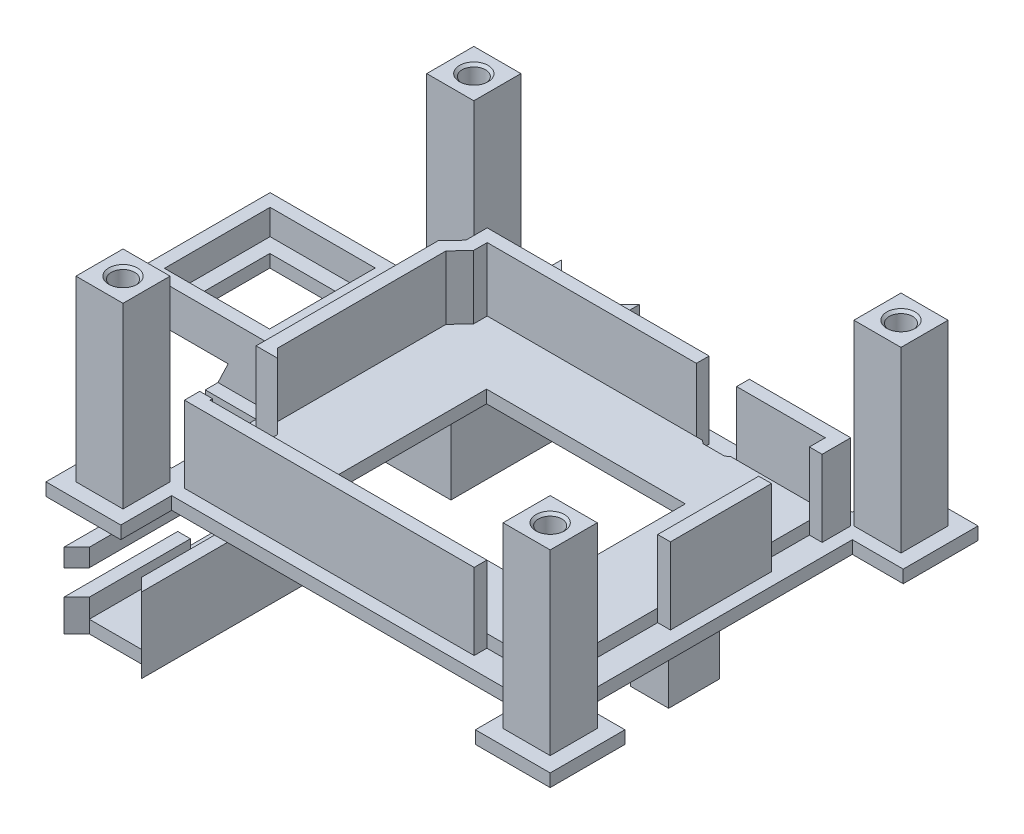
SolidWorks part; units mm, degrees
ref_plane "Front Plane" through (0, 0, 0) normal (0, 0, 1) x (1, 0, 0)
ref_plane "Top Plane" through (0, 0, 0) normal (0, 1, 0) x (1, 0, 0)
ref_plane "Right Plane" through (0, 0, 0) normal (1, 0, 0) x (0, 0, -1)
sketch "Sketch1" plane through (0, 0, 0) normal (0, -1, 0) x (1, 0, 0)
  line L0 (-32.325, 27.025) -> (34.525, 27.025)
  line L1 (34.525, 27.025) -> (34.525, -27.025)
  line L2 (34.525, -27.025) -> (-31.895, -27.025)
  line L3 (-31.895, -27.025) -> (-31.895, -24.3396)
  line L4 (-31.895, -24.3396) -> (-34.525, -21.5496)
  line L5 (-34.525, -21.5496) -> (-34.525, 11.501)
  line L6 (-34.525, 11.501) -> (-32.325, 13.751)
  line L7 (-32.325, 13.751) -> (-32.325, 27.025)
  line L8 (-32.2, 26.9) -> (34.4, 26.9) construction
  line L9 (34.4, -26.9) -> (34.4, 26.9) construction
  line L10 (16.6, -26.9) -> (34.4, -26.9) construction
  line L11 (-32.2, 13.7) -> (-32.2, 26.9) construction
  line L12 (-34.4, 11.45) -> (-32.2, 13.7) construction
  line L13 (-34.4, -21.5) -> (-34.4, 11.45) construction
  line L14 (-27.4777, 29.525) -> (37.025, 29.525)
  line L15 (37.025, 29.525) -> (37.025, -29.525)
  line L16 (37.025, -29.525) -> (-34.395, -29.525)
  line L17 (-31.77, -24.29) -> (-31.77, -26.9) construction
  line L18 (-34.4, -21.5) -> (-31.77, -24.29) construction
  line L19 (-34.395, -29.525) -> (-34.395, -25.3322)
  line L20 (-34.395, -25.3322) -> (-37.025, -22.5422)
  line L21 (-37.025, -22.5422) -> (-37.025, 14.001)
  line L22 (-37.025, 14.001) -> (-34.825, 16.251)
  line L23 (-34.825, 16.251) -> (-34.825, 29.525)
  line L24 (-34.825, 29.525) -> (-27.4777, 29.525)
  line L25 (-32.325, 26.525) -> (-34.825, 26.525)
  line L26 (9.2, -27.025) -> (17.1, -27.025)
  line L27 (9.2, -27.025) -> (9.2, -29.525)
  line L28 (9.2, -29.525) -> (17.1, -29.525)
  line L29 (17.1, -27.025) -> (17.1, -29.525)
  line L30 (-32.8139, 13.251) -> (-37.025, 13.251)
  line L32 (38.01, -14.45) -> (34.4, -14.45) construction
  line L33 (34.525, -23.9) -> (37.025, -23.9)
  line L34 (34.525, -23.9) -> (34.525, -13.95)
  line L35 (34.525, -13.95) -> (37.025, -13.95)
  line L36 (37.025, -23.9) -> (37.025, -13.95)
  line L37 (38.01, -23.4) -> (34.4, -23.4) construction
  line L38 (39.03, 17) -> (34.4, 17) construction
  line L39 (37.025, 17.5) -> (34.525, 17.5)
  line L40 (37.025, 17.5) -> (37.025, 5.9)
  line L41 (37.025, 5.9) -> (34.525, 5.9)
  line L42 (34.525, 17.5) -> (34.525, 5.9)
  line L43 (39.03, 6.4) -> (34.4, 6.4) construction
  line L44 (22.59, 26.9) -> (22.59, 22.54) construction
  line L46 (-32.325, 26.525) -> (-32.325, 16.751)
  line L48 (-34.825, 26.525) -> (-34.825, 16.751)
  line L49 (22.09, 29.525) -> (29.39, 29.525)
  line L50 (22.09, 29.525) -> (22.09, 27.025)
  line L51 (22.09, 27.025) -> (29.39, 27.025)
  line L52 (29.39, 29.525) -> (29.39, 27.025)
  line L53 (34.525, 24.8) -> (37.025, 24.8)
  line L54 (34.525, 24.8) -> (34.525, 16.8)
  line L55 (34.525, 16.8) -> (37.025, 16.8)
  line L56 (37.025, 24.8) -> (37.025, 16.8)
  line L57 (28.89, 26.9) -> (28.89, 22.54) construction
  line L58 (34.4, 24.3) -> (32.05, 24.3) construction
  line L59 (34.4, 17.3) -> (32.05, 17.3) construction
  line L72 (10.3667, -27.025) -> (11.0667, -26.5)
  line L73 (11.0667, -26.5) -> (15.2333, -26.5)
  line L74 (15.2333, -26.5) -> (15.9333, -27.025)
  line L75 (10.9, -26) -> (9.7, -26.9) construction
  line L77 (15.4, -26) -> (10.9, -26) construction
  line L79 (15.4, -26) -> (16.6, -26.9) construction
  point P72 (35.775, 24.8)
  line M6 (15.4, -26) -> (16.6, -26.9)
  line M7 (16.6, -26.9) -> (34.4, -26.9)
  line M8 (34.4, -26.9) -> (34.4, 26.9)
  line M9 (34.4, 26.9) -> (-32.2, 26.9)
  line M10 (-32.2, 26.9) -> (-32.2, 13.7)
  line M11 (-32.2, 13.7) -> (-34.4, 11.45)
  line M12 (-34.4, 11.45) -> (-34.4, -21.5)
  line M13 (-34.4, -21.5) -> (-31.77, -24.29)
  line M14 (-31.77, -24.29) -> (-31.77, -26.9)
  line M15 (-31.77, -26.9) -> (9.7, -26.9)
  line M16 (9.7, -26.9) -> (10.9, -26)
  line M17 (10.9, -26) -> (15.4, -26)
  dimension "D1" = 0.125
  dimension "D2" = 0.125
  dimension "D3" = 0.125
  dimension "D4" = 0.125
  dimension "D5" = 0.125
  dimension "D6" = 0.125
  dimension "D7" = 0.125
  dimension "D8" = 0.125
  dimension "D9" = 2.5
  dimension "D10" = 2.5
  dimension "D11" = 2.5
  dimension "D12" = 2.5
  dimension "D13" = 2.5
  dimension "D14" = 2.5
  dimension "D15" = 2.5
  dimension "D16" = 2.5
  dimension "D17" = 2.5
  dimension "D19" = 0.5
  dimension "D18" = 0.5
  dimension "D20" = 0.5
  dimension "D21" = 0.5
  dimension "D22" = 0.5
  dimension "D23" = 0.5
  dimension "D26" = 0.5
  dimension "D27" = 0.5
  dimension "D28" = 0.5
  dimension "D29" = 0.5
  dimension "D30" = 0.5
  dimension "D31" = 0.5
  dimension "D32" = 0.5
  dimension "D24" = 0.5
  dimension "D25" = 0.5
extrude "Boss-Extrude4" add sketch "Sketch1" along normal blind 2.5 contours L7 L23 L22 L21 L20 L19 L16 L27 L2 L3 L4 L5 L6 | L7 L0 L1 L39 L15 L14 L24 L23 | L33 L1 L2 L29 L16 L15 | L15 L41 L1 L35 | L1 L53 L15 L14 L52 L0 | M17 M6 M7 M8 M9 M10 M11 M12 M13 M14 M15 M16 | L7 L6 L5 L4 L3 L2 L1 L42 L0 M6 M17 M16 M15 M14 M13 M12 M11 M10 M9 M8 M7 region at (-6.6044, 0, 28.2619) region at (-5.1175, 0, 26.9373) region at (33.7869, 0, 27.7419) region at (-34.1198, 0, 12.8163) region at (35.775, 0, -4.025) region at (28.2437, 0, -27.8937) region at (0.3648, 0, -0.0614)
extrude "Boss-Extrude5" add sketch "Sketch1<5>" against normal blind 12.5 contours L24 L23 L22 L21 L20 L19 L16 L15 L14 L6 L7 L0 L1 L2 L3 L4 L5 | L50 L14 L24 L23 L25 L7 L0 | L1 L53 L15 L14 L52 L0 | L15 L41 L1 L35 | L33 L1 L2 L29 L16 L15 region at (-6.6044, 0, 28.2619) region at (33.7869, 0, 27.7419) region at (-34.1198, 0, 12.8163) region at (35.775, 0, -4.025) region at (28.2437, 0, -27.8937)
sketch "Sketch1<5>" plane through (0, 0, 0) normal (0, -1, 0) x (1, 0, 0) same geometry as "Sketch1"
sketch "Sketch2" plane through (0, 0, 0) normal (0, 1, 0) x (1, 0, 0)
  line L22 (22.09, -24.525) -> (29.39, -24.525)
  line L23 (22.09, -24.525) -> (29.39, -24.525)
  line L24 (17.1, 24.525) -> (16.7667, 24.525)
  line L25 (17.1, 24.525) -> (16.7667, 24.525)
  line L26 (9.2, 24.525) -> (-29.395, 24.525)
  line L27 (9.2, 24.525) -> (-29.395, 24.525)
  line L28 (-31.0264, -11.5032) -> (-29.825, -12.7318)
  line L29 (-31.0264, -11.5032) -> (-29.825, -12.7318)
  line L30 (32.025, 13.95) -> (32.025, 23.9)
  line L31 (32.025, 13.95) -> (32.025, 23.9)
  line L32 (32.025, 23.9) -> (32.025, 24.525)
  line L33 (32.025, 23.9) -> (32.025, 24.525)
  line L34 (32.025, 24.525) -> (17.1, 24.525)
  line L35 (32.025, 24.525) -> (17.1, 24.525)
  line L36 (-29.825, -24.525) -> (22.09, -24.525)
  line L37 (-29.825, -24.525) -> (22.09, -24.525)
  line L38 (32.025, -24.525) -> (32.025, -5.9)
  line L39 (32.025, -24.525) -> (32.025, -5.9)
  line L40 (32.025, -5.9) -> (32.025, 13.95)
  line L41 (32.025, -5.9) -> (32.025, 13.95)
  line L181 (29.39, -24.525) -> (32.025, -24.525)
  line L184 (16.7667, 24.525) -> (16.0667, 24)
  line L185 (16.0667, 24) -> (10.2333, 24)
  line L186 (10.2333, 24) -> (9.5333, 24.525)
  line L187 (9.5333, 24.525) -> (9.2, 24.525)
  line L188 (-29.395, 24.525) -> (-29.395, 23.3471)
  line L190 (-29.395, 23.3471) -> (-32.025, 20.5571)
  line L191 (-32.025, 20.5571) -> (-32.025, -10.4818)
  line L192 (-32.025, -10.4818) -> (-31.0264, -11.5032)
  line L193 (-29.825, -12.7318) -> (-29.825, -24.525)
  line L195 (29.39, -24.525) -> (32.025, -24.525)
  line L198 (16.7667, 24.525) -> (16.0667, 24)
  line L199 (16.0667, 24) -> (10.2333, 24)
  line L200 (10.2333, 24) -> (9.5333, 24.525)
  line L201 (9.5333, 24.525) -> (9.2, 24.525)
  line L202 (-29.395, 24.525) -> (-29.395, 23.3471)
  line L204 (-29.395, 23.3471) -> (-32.025, 20.5571)
  line L205 (-32.025, 20.5571) -> (-32.025, -10.4818)
  line L206 (-32.025, -10.4818) -> (-31.0264, -11.5032)
  line L207 (-29.825, -12.7318) -> (-29.825, -24.525)
  line L209 (-19.525, -14.525) -> (19.525, -14.525)
  line L210 (-19.525, -14.525) -> (-19.525, 14.525)
  line L211 (-19.525, 14.525) -> (19.525, 14.525)
  line L212 (19.525, -14.525) -> (19.525, 14.525)
  line L213 (-19.525, -14.525) -> (19.525, 14.525) construction
  line L214 (-19.525, 14.525) -> (19.525, -14.525) construction
  point P2 (0, 0)
  dimension "D1" = 2.5
extrude "Cut-Extrude1" cut sketch "Sketch2" against normal blind 12.5 contours L209 L212 L211 L210 region at (0, 0, 0)
sketch "Sketch3" plane through (0, 0, 0) normal (0, 1, 0) x (1, 0, 0)
  line L12 (-41.9, -5.7344) -> (-41.9, 15.0256)
  line L13 (-41.9, 15.0256) -> (-62.55, 15.0256)
  line L14 (-62.55, 15.0256) -> (-62.55, -5.7344)
  line L15 (-62.55, -5.7344) -> (-41.9, -5.7344)
  line L16 (-41.9, -5.7344) -> (-41.9, 15.0256)
  line L17 (-41.9, 15.0256) -> (-62.55, 15.0256)
  line L18 (-62.55, 15.0256) -> (-62.55, -5.7344)
  line L19 (-62.55, -5.7344) -> (-41.9, -5.7344)
  line L24 (-39.4, -8.2344) -> (-39.4, 17.5256)
  line L25 (-39.4, 17.5256) -> (-65.05, 17.5256)
  line L26 (-65.05, 17.5256) -> (-65.05, -8.2344)
  line L27 (-65.05, -8.2344) -> (-39.4, -8.2344)
  line L28 (-39.4, -8.2344) -> (-39.4, 17.5256)
  line L29 (-39.4, 17.5256) -> (-65.05, 17.5256)
  line L30 (-65.05, 17.5256) -> (-65.05, -8.2344)
  line L31 (-65.05, -8.2344) -> (-39.4, -8.2344)
  dimension "D1" = 0.125
  dimension "D2" = 2.625
extrude "Boss-Extrude6" add sketch "Sketch3" along normal up to surface (4.175 mm away) separate body contours L18 L19 L16 L17 | L30 L31 L28 L29 L19 L18 L17 L16 region at (-52.225, 0, -4.6456) region at (-52.225, 0, 7.8709)
extrude "Boss-Extrude7" add sketch "Sketch3<3>" along normal blind 9.17
sketch "Sketch3<3>" plane through (0, 0, 0) normal (0, 1, 0) x (1, 0, 0) same geometry as "Sketch3"
sketch "Sketch5" plane through (0, 0, 0) normal (0, -1, 0) x (1, 0, 0)
  line L1 (-65.05, 8.2344) -> (-39.4, 8.2344)
  line L2 (-65.05, 8.2344) -> (-65.05, -17.5256)
  line L3 (-65.05, -17.5256) -> (-39.4, -17.5256)
  line L4 (-39.4, 8.2344) -> (-39.4, -17.5256)
extrude "Cut-Extrude2" cut sketch "Sketch5" against normal blind 1.68
sketch "Sketch6" plane through (0, 1.68, 0) normal (0, -1, 0) x (1, 0, 0)
  line L0 (-65.05, -4.6456) -> (-39.4, -4.6456) construction
  line L1 (-59.725, -12.1456) -> (-44.725, -12.1456)
  line L2 (-59.725, -12.1456) -> (-59.725, 2.8544)
  line L3 (-59.725, 2.8544) -> (-44.725, 2.8544)
  line L4 (-44.725, -12.1456) -> (-44.725, 2.8544)
  line L5 (-59.725, -12.1456) -> (-44.725, 2.8544) construction
  line L6 (-59.725, 2.8544) -> (-44.725, -12.1456) construction
  line L7 (-65.05, 8.2344) -> (-65.05, -17.5256) construction
  line L8 (-39.4, -17.5256) -> (-39.4, 8.2344) construction
  line L9 (-52.225, 8.2344) -> (-52.225, -17.5256) construction
  line L10 (-39.4, 8.2344) -> (-65.05, 8.2344) construction
  line L11 (-65.05, -17.5256) -> (-39.4, -17.5256) construction
  point P0 (-52.225, -4.6456)
  point P18 (-52.225, -4.6456)
  dimension "D1" = 15
extrude "Cut-Extrude3" cut sketch "Sketch6" against normal up to next (2.495 mm away)
sketch "Sketch7" plane through (-39.4, 0, 0) normal (1, 0, 0) x (0, 0, -1)
  line L0 (-8.2344, 9.17) -> (17.5256, 9.17) construction
  line L1 (-8.2344, 9.17) -> (17.5256, 9.17)
  line L2 (-8.2344, 9.17) -> (-8.2344, 1.68)
  line L3 (-8.2344, 1.68) -> (17.5256, 1.68)
  line L4 (17.5256, 9.17) -> (17.5256, 1.68)
  line L5 (-8.2344, 9.17) -> (-8.2344, 1.68) construction
extrude "Boss-Extrude8" add sketch "Sketch7" along normal up to next
sketch "Sketch8" plane through (0, -2.5, 0) normal (0, -1, 0) x (1, 0, 0)
  line L31 (-34.825, 29.525) -> (22.09, 29.525) construction
  line L32 (-49.525, -42.025) -> (49.525, -42.025)
  line L33 (-49.525, -42.025) -> (-49.525, 42.025)
  line L34 (-49.525, 42.025) -> (49.525, 42.025)
  line L35 (49.525, -42.025) -> (49.525, 42.025)
  line L36 (-49.525, -42.025) -> (49.525, 42.025) construction
  line L37 (-49.525, 42.025) -> (49.525, -42.025) construction
  line L39 (37.025, 5.9) -> (37.025, -13.95) construction
  line L40 (19.525, 14.525) -> (-19.525, 14.525) construction
  line L41 (-24.525, 19.525) -> (24.525, 19.525)
  line L42 (-24.525, 19.525) -> (-24.525, -19.525)
  line L43 (-24.525, -19.525) -> (24.525, -19.525)
  line L44 (24.525, 19.525) -> (24.525, -19.525)
  line L45 (-24.525, 19.525) -> (24.525, -19.525) construction
  line L46 (-24.525, -19.525) -> (24.525, 19.525) construction
  line L47 (19.525, -14.525) -> (19.525, 14.525) construction
  point P2 (0, 0)
  point P7 (0, 0)
  dimension "D1" = 12.5
  dimension "D2" = 12.5
  dimension "D3" = 5
  dimension "D4" = 5
extrude "Boss-Extrude10" add sketch "Sketch8" along normal blind 2.5
sketch "Sketch9" plane through (0, 0, -17.5256) normal (0, 0, -1) x (-1, 0, 0)
  line L0 (47.5344, 1.68) -> (37.025, 1.68)
  line L2 (37.025, 1.68) -> (37.025, -2.5)
  line L3 (49.525, -2.5) -> (-49.525, -2.5) construction
  line L4 (49.525, -2.5) -> (47.5344, 1.68)
  line L5 (37.025, -2.5) -> (37.025, 12.5) construction
  line L6 (37.025, -2.5) -> (49.525, -2.5)
extrude "Boss-Extrude11" add sketch "Sketch9" against normal up to surface (25.76 mm away) up to face at (-51.0375, 5.425, 8.2344)
sketch "Sketch10" plane through (0, -2.5, 0) normal (0, 1, 0) x (1, 0, 0)
  line L0 (-34.395, 29.525) -> (-34.395, 25.3322) construction
  line L1 (-46.585, 29.835) -> (-37.335, 29.835)
  line L2 (-46.585, 29.835) -> (-46.585, 39.085)
  line L3 (-46.585, 39.085) -> (-37.335, 39.085)
  line L4 (-37.335, 29.835) -> (-37.335, 39.085)
  line L5 (-46.585, 29.835) -> (-37.335, 39.085) construction
  line L6 (-46.585, 39.085) -> (-37.335, 29.835) construction
  line L7 (-49.525, 42.025) -> (-34.395, 42.025)
  line L8 (-49.525, 42.025) -> (-49.525, 26.895)
  line L9 (-49.525, 26.895) -> (-34.395, 26.895)
  line L10 (-34.395, 42.025) -> (-34.395, 26.895)
  line L11 (-41.96, 26.895) -> (-41.96, 42.025) construction
  line L12 (-49.525, 34.46) -> (-34.395, 34.46) construction
  line L13 (0, 42.025) -> (0, -42.025) construction
  line L14 (-49.525, 42.025) -> (49.525, 42.025) construction
  line L15 (49.525, -42.025) -> (-49.525, -42.025) construction
  line L16 (49.525, 0) -> (-42.025, 0) construction
  line L17 (49.525, 42.025) -> (49.525, -42.025) construction
  line L18 (-42.025, -5.6094) -> (-42.025, 14.9006) construction
  line L19 (46.585, 29.835) -> (37.335, 29.835)
  line L20 (46.585, 29.835) -> (46.585, 39.085)
  line L21 (46.585, 39.085) -> (37.335, 39.085)
  line L22 (37.335, 29.835) -> (37.335, 39.085)
  line L23 (-46.585, -29.835) -> (-37.335, -29.835)
  line L24 (-37.335, -29.835) -> (-37.335, -39.085)
  line L25 (-46.585, -39.085) -> (-37.335, -39.085)
  line L26 (-46.585, -29.835) -> (-46.585, -39.085)
  line L27 (46.585, -29.835) -> (37.335, -29.835)
  line L28 (37.335, -29.835) -> (37.335, -39.085)
  line L29 (46.585, -39.085) -> (37.335, -39.085)
  line L30 (46.585, -29.835) -> (46.585, -39.085)
  line L32 (-37.335, 39.085) -> (37.335, 39.085)
  line L33 (-37.335, 39.085) -> (-37.335, 29.835)
  line L34 (-37.335, 29.835) -> (37.335, 29.835)
  line L35 (37.335, 39.085) -> (37.335, 29.835)
  line L36 (0, 29.835) -> (0, 39.085) construction
  line L37 (-37.335, 34.46) -> (37.335, 34.46) construction
  line L38 (-37.335, -29.835) -> (37.335, -29.835)
  line L39 (-37.335, -29.835) -> (-37.335, -39.085)
  line L40 (-37.335, -39.085) -> (37.335, -39.085)
  line L41 (37.335, -29.835) -> (37.335, -39.085)
  line L42 (0, -39.085) -> (0, -29.835) construction
  line L43 (-37.335, -34.46) -> (37.335, -34.46) construction
  point P0 (-41.96, 34.46)
  point P204 (0, 34.46)
  point P209 (0, -34.46)
  point P993 (-41.96, 34.46)
  line M21 (17.1, 29.525) -> (37.025, 29.525)
  line M22 (37.025, 29.525) -> (37.025, 23.9)
  line M30 (37.025, -24.8) -> (37.025, -29.525)
  line M31 (37.025, -29.525) -> (29.39, -29.525)
  dimension "D1" = 9.25
  dimension "D2" = 9.25
extrude "Boss-Extrude12" add sketch "Sketch10" along normal blind 35 contours L1 L4 L3 L2 | L22 L19 L20 L21 M21 M22 | L30 L27 L28 L29 M30 M31 | L23 L26 L25 L24 region at (-41.96, -2.5, -34.46) region at (41.96, -2.5, -34.46) region at (-41.96, -2.5, 34.46) region at (41.96, -2.5, 34.46)
sketch "Sketch11" plane through (0, 32.5, 0) normal (0, 1, 0) x (1, 0, 0)
  line L0 (-41.96, 39.085) -> (-41.96, 29.835)
  line L1 (-46.585, 39.085) -> (-37.335, 39.085) construction
  line L2 (-46.585, 29.835) -> (-37.335, 29.835) construction
  line L3 (-44.26, 34.46) -> (-44.26, 39.085)
  line L4 (-46.585, 29.835) -> (-46.585, 39.085) construction
  line L5 (-46.585, 34.46) -> (-37.335, 34.46)
  line L6 (-37.335, 29.835) -> (-37.335, 39.085) construction
  line L7 (-81.725, 0) -> (81.725, 0) construction
  line L8 (0, 67.5081) -> (0, -67.5081) construction
  circle A0 centre (-41.96, 34.46) radius 2.3
  circle A1 centre (41.96, 34.46) radius 2.3
  circle A2 centre (41.96, -34.46) radius 2.3
  circle A3 centre (-41.96, -34.46) radius 2.3
  point P20 (0, 0)
  point P24 (0, 0)
  dimension "D1" = 4.6
extrude "Cut-Extrude5" cut sketch "Sketch11" against normal blind 6.2 contours L5 A0 L0 | L0 A0 L5 | L5 A0 L0 | L0 A0 L5 | A3 | A2 | A1 region at (-40.9838, 32.5, -35.4362) region at (-42.9362, 32.5, -35.4362) region at (-40.9838, 32.5, -33.4838) region at (-42.9362, 32.5, -33.4838) region at (41.96, 32.5, -34.46) region at (41.96, 32.5, 34.46) region at (-41.96, 32.5, 34.46)
chamfer "Chamfer3" distance 0.5 angle 45 4 edges at (41.96, 32.5, 36.76) (41.96, 32.5, -32.16) (-41.96, 32.5, -32.16) (-41.96, 32.5, 36.76)
sketch "Sketch13" plane through (0, -2.5, 0) normal (0, 1, 0) x (1, 0, 0)
  line L0 (-49.525, 42.025) -> (49.525, 42.025) construction
  line L1 (-34.835, 42.025) -> (34.835, 42.025)
  line L2 (-34.835, 42.025) -> (-34.835, 32.025)
  line L3 (-34.835, 32.025) -> (34.835, 32.025)
  line L4 (34.835, 42.025) -> (34.835, 32.025)
  line L5 (0, 32.025) -> (0, 42.025) construction
  line L6 (-34.835, 37.025) -> (34.835, 37.025) construction
  line L7 (39.525, 27.335) -> (49.525, 27.335)
  line L8 (39.525, 27.335) -> (39.525, -27.335)
  line L9 (39.525, -27.335) -> (49.525, -27.335)
  line L10 (49.525, 27.335) -> (49.525, -27.335)
  line L11 (44.525, -27.335) -> (44.525, 27.335) construction
  line L12 (39.525, 0) -> (49.525, 0) construction
  line L13 (-34.835, -32.025) -> (34.835, -32.025)
  line L14 (-34.835, -32.025) -> (-34.835, -42.025)
  line L15 (-34.835, -42.025) -> (34.835, -42.025)
  line L16 (34.835, -32.025) -> (34.835, -42.025)
  line L17 (0, -42.025) -> (0, -32.025) construction
  line L18 (-34.835, -37.025) -> (34.835, -37.025) construction
  line L19 (-49.525, -10.7344) -> (-39.525, -10.7344)
  line L20 (-49.525, -10.7344) -> (-49.525, -27.335)
  line L21 (-49.525, -27.335) -> (-39.525, -27.335)
  line L22 (-39.525, -10.7344) -> (-39.525, -27.335)
  line L23 (-44.525, -27.335) -> (-44.525, -10.7344) construction
  line L24 (-49.525, -19.0347) -> (-39.525, -19.0347) construction
  line L25 (-49.525, 27.335) -> (-39.525, 27.335)
  line L26 (-49.525, 27.335) -> (-49.525, 20.0256)
  line L27 (-49.525, 20.0256) -> (-39.525, 20.0256)
  line L28 (-39.525, 27.335) -> (-39.525, 20.0256)
  line L29 (-44.525, 20.0256) -> (-44.525, 27.335) construction
  line L30 (-49.525, 23.6803) -> (-39.525, 23.6803) construction
  line L31 (9.2, 29.525) -> (-34.395, 29.525) construction
  line L32 (-37.335, 29.835) -> (-37.335, 39.085) construction
  line L33 (37.335, 29.835) -> (37.335, 39.085) construction
  line L34 (49.525, 42.025) -> (49.525, -42.025) construction
  line L35 (46.585, 29.835) -> (37.335, 29.835) construction
  line L36 (46.585, -29.835) -> (37.335, -29.835) construction
  line L37 (37.025, 23.9) -> (37.025, 29.525) construction
  line L38 (37.335, -29.835) -> (37.335, -39.085) construction
  line L39 (-34.825, -29.525) -> (22.09, -29.525) construction
  line L40 (-37.335, -29.835) -> (-37.335, -39.085) construction
  line L41 (49.525, -42.025) -> (-49.525, -42.025) construction
  line L42 (-49.525, -42.025) -> (-49.525, -8.2344) construction
  line L43 (-37.025, 22.5422) -> (-37.025, -13.251) construction
  line L44 (-46.585, -29.835) -> (-37.335, -29.835) construction
  line L45 (-49.525, -8.2344) -> (-37.025, -8.2344) construction
  line L46 (-37.025, 17.5256) -> (-49.525, 17.5256) construction
  line L47 (-46.585, 29.835) -> (-37.335, 29.835) construction
  line L48 (-37.025, 22.5422) -> (-37.025, 17.5256) construction
  line L49 (-49.525, 17.5256) -> (-49.525, 42.025) construction
  point P80 (-44.525, 23.6803)
  point P104 (44.525, 0)
  point P116 (0, 37.025)
  point P138 (0, -37.025)
  point P155 (-44.525, -19.0347)
  dimension "D1" = 0
  dimension "D2" = 2.5
  dimension "D3" = 2.5
  dimension "D4" = 2.5
  dimension "D5" = 0
  dimension "D6" = 2.5
  dimension "D7" = 2.5
  dimension "D8" = 2.5
  dimension "D9" = 2.5
  dimension "D10" = 2.5
  dimension "D11" = 2.5
  dimension "D12" = 0
  dimension "D13" = 0
  dimension "D14" = 2.5
  dimension "D15" = 2.5
  dimension "D16" = 2.5
  dimension "D17" = 2.5
  dimension "D18" = 2.5
  dimension "D19" = 2.5
  dimension "D20" = 0
extrude "Cut-Extrude6" cut sketch "Sketch13" against normal blind 10
sketch "Sketch14" plane through (0, -5, 0) normal (0, -1, 0) x (1, 0, 0)
  line L1 (-39.15, 48.9) -> (-39.15, 11.9)
  line L2 (-39.15, 11.9) -> (-23.9, 11.9)
  line L3 (-23.9, 11.9) -> (-23.9, 48.9)
  line L8 (-39.15, -11.9) -> (-39.15, -48.9)
  line L10 (-23.9, -48.9) -> (-23.9, -11.9)
  line L11 (-23.9, -11.9) -> (-39.15, -11.9)
  line L12 (-36.65, -46.4) -> (-26.4, -46.4)
  line L13 (-26.4, -46.4) -> (-26.4, -14.4)
  line L14 (-26.4, -14.4) -> (-36.65, -14.4)
  line L15 (-36.65, -14.4) -> (-36.65, -46.4)
  line L16 (-26.4, 46.4) -> (-36.65, 46.4)
  line L17 (-36.65, 46.4) -> (-36.65, 14.4)
  line L18 (-36.65, 14.4) -> (-26.4, 14.4)
  line L19 (-26.4, 14.4) -> (-26.4, 46.4)
  line L21 (-36.65, 46.4) -> (-36.65, 14.4)
  line L22 (-36.65, 14.4) -> (-26.4, 14.4)
  line L23 (-26.4, 14.4) -> (-26.4, 46.4)
  line L25 (-26.4, -46.4) -> (-26.4, -14.4)
  line L26 (-26.4, -14.4) -> (-36.65, -14.4)
  line L27 (-36.65, -14.4) -> (-36.65, -46.4)
  line L44 (-23.9, 48.9) -> (-39.15, 48.9) construction
  line L45 (-26.4, 46.4) -> (-36.65, 46.4) construction
  line L46 (-39.15, 48.9) -> (-36.65, 46.4)
  line L47 (-26.4, 46.4) -> (-23.9, 48.9)
  line L48 (-26.4, -46.4) -> (-23.9, -48.9)
  line L49 (-39.15, -48.9) -> (-23.9, -48.9) construction
  line L50 (-36.65, -46.4) -> (-26.4, -46.4) construction
  line L51 (-36.65, -46.4) -> (-39.15, -48.9)
  dimension "D1" = 0.125
  dimension "D2" = 2.5
  dimension "D3" = 0.125
  dimension "D4" = 2.5
extrude "Boss-Extrude13" add sketch "Sketch14" along normal blind 12.25
sketch "Sketch16" plane through (0, -17.25, 0) normal (0, -1, 0) x (1, 0, 0)
  line L0 (-39.15, 48.9) -> (-36.65, 46.4)
  line L1 (-36.65, 46.4) -> (-36.65, 14.4)
  line L2 (-36.65, 14.4) -> (-26.4, 14.4)
  line L3 (-26.4, 14.4) -> (-26.4, 46.4)
  line L4 (-26.4, 46.4) -> (-23.9, 48.9)
  line L5 (-23.9, 48.9) -> (-23.9, 11.9)
  line L6 (-39.15, 11.9) -> (-23.9, 11.9) construction
  line L7 (-23.9, 11.9) -> (-23.9, 48.9) construction
  line L8 (-23.9, 11.9) -> (-39.15, 11.9)
  line L9 (-39.15, 48.9) -> (-39.15, 11.9) construction
  line L18 (-36.65, -46.4) -> (-26.4, -46.4)
  line L19 (-36.65, 46.4) -> (-26.4, 46.4)
  line L26 (-23.9, -11.9) -> (-39.15, -11.9)
  line L27 (-39.15, -11.9) -> (-39.15, -48.9)
  line L28 (-39.15, -48.9) -> (-36.65, -46.4)
  line L29 (-36.65, -46.4) -> (-36.65, -14.4)
  line L30 (-36.65, -14.4) -> (-26.4, -14.4)
  line L31 (-26.4, -14.4) -> (-26.4, -46.4)
  line L32 (-26.4, -46.4) -> (-23.9, -48.9)
  line L33 (-23.9, -48.9) -> (-23.9, -11.9)
  line L34 (-23.9, -11.9) -> (-39.15, -11.9)
  line L35 (-39.15, -11.9) -> (-39.15, -48.9)
  line L36 (-39.15, -48.9) -> (-36.65, -46.4)
  line L37 (-36.65, -46.4) -> (-36.65, -14.4)
  line L38 (-36.65, -14.4) -> (-26.4, -14.4)
  line L39 (-26.4, -14.4) -> (-26.4, -46.4)
  line L40 (-26.4, -46.4) -> (-23.9, -48.9)
  line L41 (-23.9, -48.9) -> (-23.9, -11.9)
  line M9 (-23.9, 48.9) -> (-26.4, 46.4)
  line M10 (-26.4, 46.4) -> (-26.4, 14.4)
  line M11 (-26.4, 14.4) -> (-36.65, 14.4)
  line M12 (-36.65, 14.4) -> (-36.65, 46.4)
  line M13 (-36.65, 46.4) -> (-39.15, 48.9)
  line M14 (-39.15, 48.9) -> (-39.15, 11.9)
  line M15 (-39.15, 11.9) -> (-23.9, 11.9)
  line M16 (-23.9, 11.9) -> (-23.9, 48.9)
  dimension "D1" = 0
extrude "Boss-Extrude15" add sketch "Sketch16" along normal blind 2.5 contours M16 M9 M10 M11 M12 M13 M14 M15 | L40 L41 L34 L35 L36 L37 L38 L39 | L19 M12 M11 M10 | L39 L38 L37 L18 region at (-38.183, -17.25, 47.367) region at (-31.525, -17.25, 30.4) region at (-31.525, -17.25, -30.4) region at (-38.183, -17.25, -47.367)
sketch "Sketch18" plane through (-36.525, 0, 0) normal (-1, 0, 0) x (0, 0, 1)
  line L0 (-14.525, -17.125) -> (-46.275, -17.125) construction
  line L1 (-17.525, -17.125) -> (-26.525, -17.125)
  line L2 (-17.525, -17.125) -> (-17.525, -5.125)
  line L3 (-17.525, -5.125) -> (-26.525, -5.125)
  line L4 (-26.525, -17.125) -> (-26.525, -5.125)
  line L5 (-22.025, -5.125) -> (-22.025, -17.125) construction
  line L6 (-17.525, -11.125) -> (-26.525, -11.125) construction
  line L7 (-14.525, -5.125) -> (-46.275, -5.125) construction
  line L8 (46.275, -17.125) -> (14.525, -17.125) construction
  line L9 (26.525, -17.125) -> (17.525, -17.125)
  line L10 (26.525, -17.125) -> (26.525, -5.125)
  line L11 (26.525, -5.125) -> (17.525, -5.125)
  line L12 (17.525, -17.125) -> (17.525, -5.125)
  line L13 (22.025, -5.125) -> (22.025, -17.125) construction
  line L14 (26.525, -11.125) -> (17.525, -11.125) construction
  line L15 (46.275, -5.125) -> (14.525, -5.125) construction
  line L16 (-14.525, -17.125) -> (-14.525, -5.125) construction
  line L17 (14.525, -17.125) -> (14.525, -5.125) construction
  point P232 (22.025, -11.125)
  point P292 (-22.025, -11.125)
  dimension "D1" = 3
  dimension "D2" = 3
  dimension "D3" = 12
  dimension "D4" = 12
extrude "Cut-Extrude9" cut sketch "Sketch18" along normal through all
sketch "Sketch21" plane through (-39.15, 0, 0) normal (-1, 0, 0) x (0, 0, 1)
  line L0 (-26.525, -5.125) -> (-26.525, -17.125) construction
  line L1 (-26.525, -8.5) -> (-48.9, -8.5)
  line L2 (-26.525, -8.5) -> (-26.525, -13.5)
  line L3 (-26.525, -13.5) -> (-48.9, -13.5)
  line L4 (-48.9, -8.5) -> (-48.9, -13.5)
  line L5 (-37.7125, -13.5) -> (-37.7125, -8.5) construction
  line L6 (-26.525, -11) -> (-48.9, -11) construction
  line L7 (-48.9, -19.75) -> (-48.9, -5) construction
  line L8 (-27.335, -5) -> (-42.025, -5) construction
  line L9 (26.525, -17.125) -> (26.525, -5.125) construction
  line L10 (26.525, -8.5) -> (48.9, -8.5)
  line L11 (26.525, -8.5) -> (26.525, -13.5)
  line L12 (26.525, -13.5) -> (48.9, -13.5)
  line L13 (48.9, -8.5) -> (48.9, -13.5)
  line L14 (37.7125, -13.5) -> (37.7125, -8.5) construction
  line L15 (26.525, -11) -> (48.9, -11) construction
  line L16 (48.9, -19.75) -> (48.9, -5) construction
  line L17 (48.9, -5) -> (42.025, -5) construction
  point P132 (-37.7125, -11)
  point P195 (37.7125, -11)
  dimension "D1" = 5
  dimension "D2" = 3.5
  dimension "D3" = 5
  dimension "D4" = 3.5
extrude "Cut-Extrude10" cut sketch "Sketch21" against normal up to next
sketch "Sketch22" plane through (0, 0, 56.275) normal (0, 0, 1) x (1, 0, 0)
  circle A0 centre (-31.525, -11.0625) radius 16
  circle A1 centre (-31.2344, -18.3067) radius 8.75
sketch "Sketch23" plane through (0, -5, 0) normal (0, -1, 0) x (1, 0, 0)
  line L0 (39.525, 0) -> (24.525, 0) construction
  line L1 (39.525, -27.335) -> (39.525, 27.335) construction
  line L2 (24.525, -19.525) -> (24.525, 19.525) construction
  line L4 (28.275, 5) -> (35.775, 5)
  line L5 (28.275, 5) -> (28.275, -5)
  line L6 (28.275, -5) -> (35.775, -5)
  line L7 (35.775, 5) -> (35.775, -5)
  line L8 (28.275, 5) -> (35.775, -5) construction
  line L9 (28.275, -5) -> (35.775, 5) construction
  point P8 (32.025, 0)
  dimension "D1" = 7.5
  dimension "D2" = 10
extrude "Boss-Extrude17" add sketch "Sketch23" along normal blind 11.9
equation "\"SlideClearance\"= 0.125mm"
equation "\"D5@Sketch1\"=\"SlideClearance\""
equation "\"D4@Sketch1\"=\"SlideClearance\""
equation "\"D2@Sketch1\"=\"SlideClearance\""
equation "\"D1@Sketch1\"=\"SlideClearance\""
equation "\"D3@Sketch1\"=\"SlideClearance\""
equation "\"D6@Sketch1\"=\"SlideClearance\""
equation "\"D7@Sketch1\"=\"SlideClearance\""
equation "\"D8@Sketch1\"=\"SlideClearance\""
equation "\"ShellWidth\"= 2.5mm"
equation "\"D9@Sketch1\"=\"ShellWidth\""
equation "\"D10@Sketch1\"=\"ShellWidth\""
equation "\"D11@Sketch1\"=\"ShellWidth\""
equation "\"D12@Sketch1\"=\"ShellWidth\""
equation "\"D13@Sketch1\"=\"ShellWidth\""
equation "\"D14@Sketch1\"=\"ShellWidth\""
equation "\"D15@Sketch1\"=\"ShellWidth\""
equation "\"D16@Sketch1\"=\"ShellWidth\""
equation "\"D17@Sketch1\"=\"ShellWidth\""
equation "\"OpeningGap\"= 0.5mm"
equation "\"D19@Sketch1\"=\"OpeningGap\""
equation "\"D18@Sketch1\"=\"OpeningGap\""
equation "\"D20@Sketch1\"=\"OpeningGap\""
equation "\"D21@Sketch1\"=\"OpeningGap\""
equation "\"D22@Sketch1\"=\"OpeningGap\""
equation "\"D23@Sketch1\"=\"OpeningGap\""
equation "\"D26@Sketch1\"=\"OpeningGap\""
equation "\"D27@Sketch1\"=\"OpeningGap\""
equation "\"D28@Sketch1\"=\"OpeningGap\""
equation "\"D29@Sketch1\"=\"OpeningGap\""
equation "\"D30@Sketch1\"=\"OpeningGap\""
equation "\"Chamfer\"= 0.1mm"
equation "\"D1@Sketch3\"=\"SlideClearance\""
equation "\"D2@Sketch3\"=\"SlideClearance\" + \"ShellWidth\""
